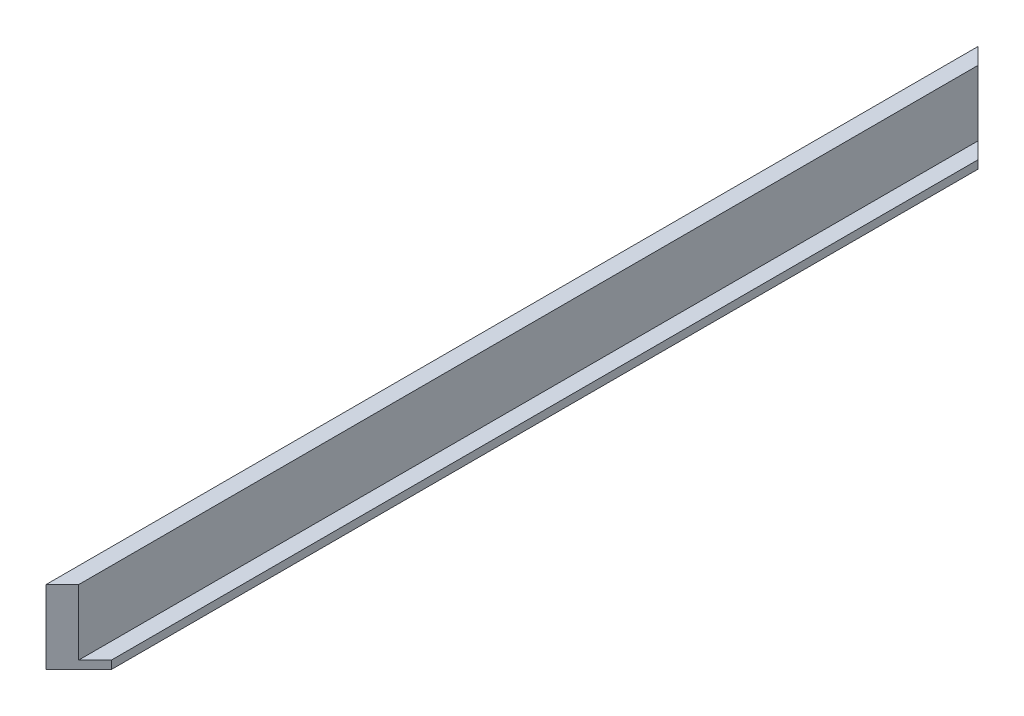
SolidWorks part; units mm, degrees
ref_plane "Plan de face" through (0, 0, 0) normal (0, 0, 1) x (1, 0, 0)
ref_plane "Plan de dessus" through (0, 0, 0) normal (0, 1, 0) x (1, 0, 0)
ref_plane "Plan de droite" through (0, 0, 0) normal (1, 0, 0) x (0, 0, -1)
sketch "Esquisse1" plane through (0, 0, 0) normal (0, 0, 1) x (1, 0, 0)
  line L0 (-10, 40) -> (-10, -5)
  line L1 (-10, -5) -> (10, -5)
  line L2 (10, -5) -> (10, 0)
  line L3 (10, 0) -> (0, 0)
  line L4 (0, 0) -> (0, 40)
  line L5 (0, 40) -> (-10, 40)
  point P2 (0, 0)
  dimension "D1" = 10
  dimension "D2" = 5
  dimension "D3" = 10
  dimension "D4" = 40
extrude "Boss.-Extru.1" add sketch "Esquisse1" along normal mid plane 600
sketch "Esquisse2" plane through (0, -5, 0) normal (0, -1, 0) x (1, 0, 0)
  line L0 (10, 265) -> (-10, 285)
  line L1 (10, 300) -> (10, -300) construction
  line L2 (-10, 300) -> (-10, -300) construction
  line L3 (-10, 285) -> (-10, 300)
  line L4 (-10, 300) -> (10, 300)
  line L5 (10, 300) -> (10, 265)
  line L6 (0, 300) -> (0, -300) construction
  point P6 (0, 275)
  dimension "D1" = 275
  dimension "D2" = 45
extrude "Enlèv. mat.-Extru.1" cut sketch "Esquisse2" against normal through all both and the other way through all
mirror "Symétrie1" about plane through (0, 0, 0) normal (0, 0, 1) of "Enlèv. mat.-Extru.1"
